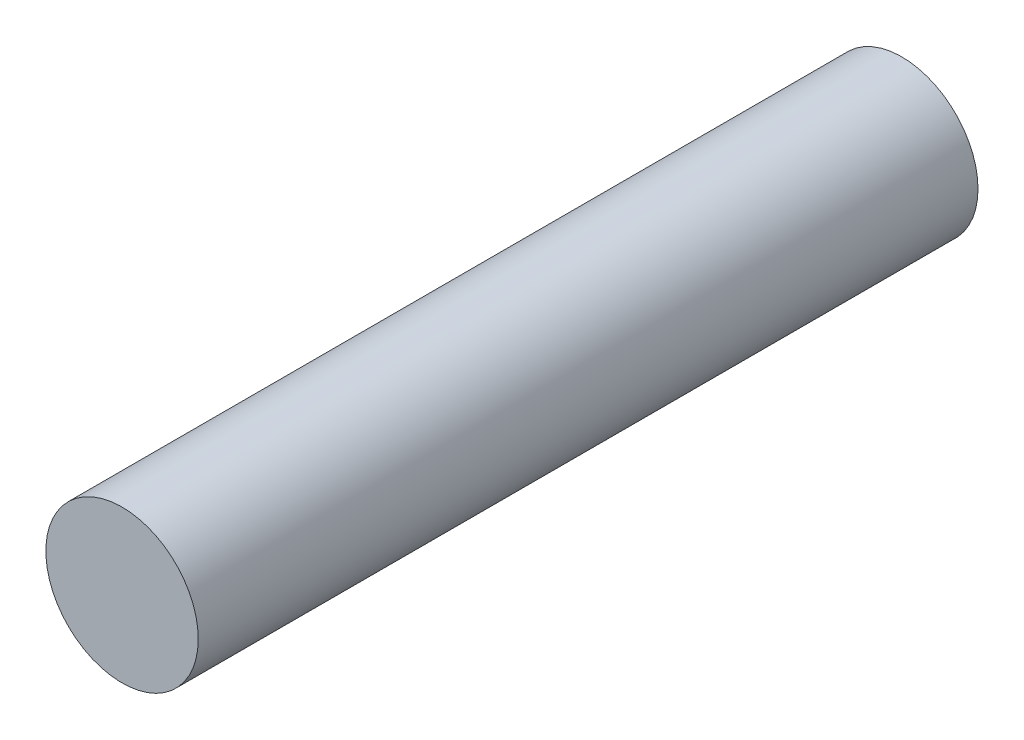
SolidWorks part; units mm, degrees
ref_plane "Front Plane" through (0, 0, 0) normal (0, 0, 1) x (1, 0, 0)
ref_plane "Top Plane" through (0, 0, 0) normal (0, 1, 0) x (1, 0, 0)
ref_plane "Right Plane" through (0, 0, 0) normal (1, 0, 0) x (0, 0, -1)
sketch "Sketch1" plane through (0, 0, 0) normal (0, 0, 1) x (1, 0, 0)
  circle A0 centre (0, 0) radius 3
  dimension "D1" = 6
extrude "Boss-Extrude1" add sketch "Sketch1" along normal blind 30.7 contours A0
equation "\"ShaftDiameter\"= 12mm"
equation "\"PendulumDiameter\"=12mm"
equation "\"EncoderShaftDiameter\"= 6mm"
equation "\"D1@Sketch1\"=\"EncoderShaftDiameter\""
equation "\"EncoderShaftLength\"=15mm+.5in+3mm"
equation "\"D1@Boss-Extrude1\"=\"EncoderShaftLength\""
